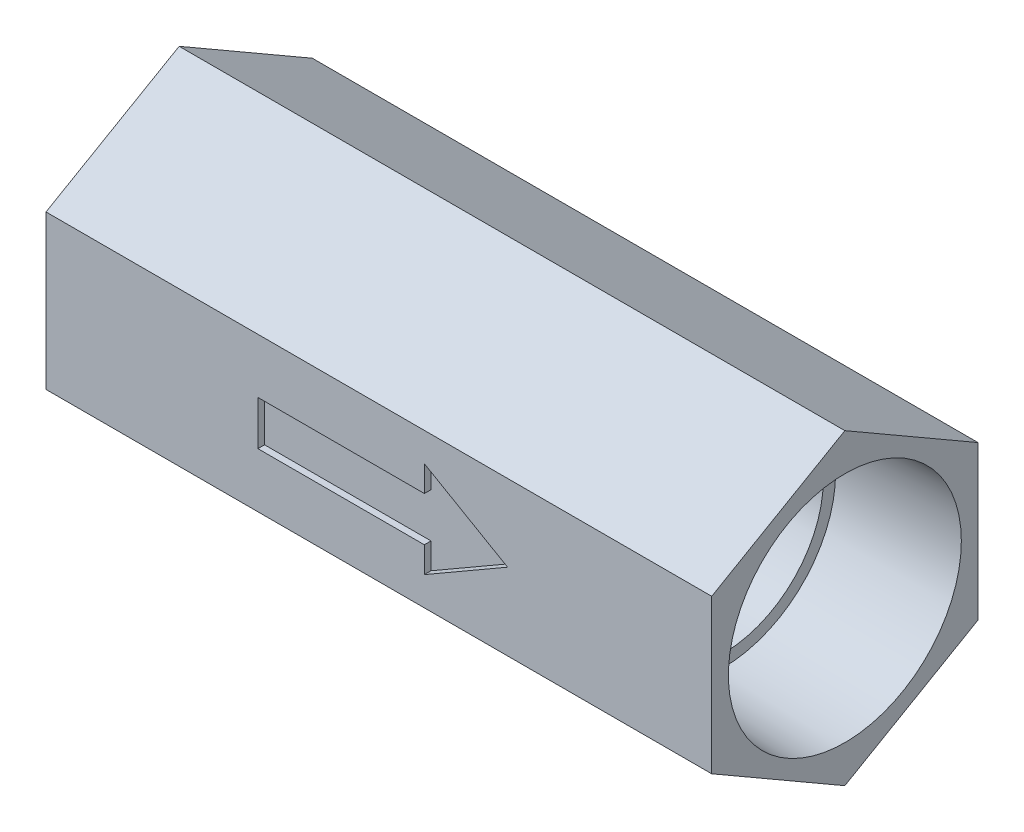
SolidWorks part; units mm, degrees
ref_plane "Front Plane" through (0, 0, 0) normal (0, 0, 1) x (1, 0, 0)
ref_plane "Top Plane" through (0, 0, 0) normal (0, 1, 0) x (1, 0, 0)
ref_plane "Right Plane" through (0, 0, 0) normal (1, 0, 0) x (0, 0, -1)
sketch "Sketch1" plane through (0, 0, 0) normal (1, 0, 0) x (0, 0, -1)
  line L1 (0, 17.5976) -> (-15.24, 8.7988)
  line L2 (-15.24, 8.7988) -> (-15.24, -8.7988)
  line L3 (-15.24, -8.7988) -> (0, -17.5976)
  line L4 (0, -17.5976) -> (15.24, -8.7988)
  line L5 (15.24, -8.7988) -> (15.24, 8.7988)
  line L6 (15.24, 8.7988) -> (0, 17.5976)
  circle A0 centre (0, 0) radius 15.24 construction
  dimension "D1" = 30.48
extrude "Boss-Extrude1" add sketch "Sketch1" along normal blind 38.1 and the other way blind 38.1
sketch "Sketch2" plane through (38.1, 0, 0) normal (1, 0, 0) x (0, 0, -1)
  point P0 (0, 0)
hole_wizard "3/4 NPT Tapped Hole1" positions "Sketch3" profile "Sketch4" size "3/4" standard "ANSI Inch"
sketch "Sketch3" plane through (38.1, 0, 0) normal (1, 0, 0) x (0, 0, -1)
  point P0 (0, 0)
sketch "Sketch4" plane through (38.1, 0, 0) normal (0, 1, 0) x (0, 0, -1)
  line L0 (0, 0) -> (0, 24.6936)
  line L1 (11.5062, 17.78) -> (0, 24.6936)
  line L2 (-11.5062, 17.78) -> (0, 24.6936) construction
  line L3 (11.5062, 17.78) -> (11.5062, 13.97)
  line L4 (11.5062, 13.97) -> (12.9142, 13.97)
  line L5 (12.9142, 13.97) -> (13.3325, 0)
  line L6 (-12.9142, 13.97) -> (-13.3325, 0) construction
  line L7 (13.3325, 0) -> (0, 0)
  line L8 (0, -6.35) -> (0, 107.95) construction
  line L11 (-11.5062, 13.97) -> (-12.9142, 13.97) construction
  dimension "Tap Drill Dia." = 23.0124
  dimension "Tap Drill Depth" = 17.78
  dimension "Thread Dia." = 26.665
  dimension "Thread Angle" = 3.43
  dimension "Thread Depth" = 13.97
  dimension "Drill Angle" = 118
sketch "Sketch5" plane through (-38.1, 0, 0) normal (-1, 0, 0) x (0, 0, 1)
  point P0 (0, 0)
  point P1 (0, 0)
  point P3 (0, 0)
hole_wizard "3/4 NPT Tapped Hole2" positions "Sketch8" profile "Sketch9" size "3/4" standard "ANSI Inch"
sketch "Sketch8" plane through (-38.1, 0, 0) normal (-1, 0, 0) x (0, 0, 1)
  point P0 (0, 0)
sketch "Sketch9" plane through (-38.1, 0, 0) normal (0, 1, 0) x (0, 0, 1)
  line L0 (0, 0) -> (0, 24.6936)
  line L1 (11.5062, 17.78) -> (0, 24.6936)
  line L2 (-11.5062, 17.78) -> (0, 24.6936) construction
  line L3 (11.5062, 17.78) -> (11.5062, 13.97)
  line L4 (11.5062, 13.97) -> (12.9142, 13.97)
  line L5 (12.9142, 13.97) -> (13.3325, 0)
  line L6 (-12.9142, 13.97) -> (-13.3325, 0) construction
  line L7 (13.3325, 0) -> (0, 0)
  line L8 (0, -6.35) -> (0, 107.95) construction
  line L11 (-11.5062, 13.97) -> (-12.9142, 13.97) construction
  dimension "Tap Drill Dia." = 23.0124
  dimension "Tap Drill Depth" = 17.78
  dimension "Thread Dia." = 26.665
  dimension "Thread Angle" = 3.43
  dimension "Thread Depth" = 13.97
  dimension "Drill Angle" = 118
sketch "Sketch10" plane through (0, 0, 15.24) normal (0, 0, 1) x (1, 0, 0)
  line L1 (-13.843, -2.54) -> (5.207, -2.54)
  line L2 (-13.843, -2.54) -> (-13.843, 2.54)
  line L3 (-13.843, 2.54) -> (5.207, 2.54)
  line L4 (5.207, -2.54) -> (5.207, 2.54)
  line L5 (-13.843, -2.54) -> (5.207, 2.54) construction
  line L6 (-13.843, 2.54) -> (5.207, -2.54) construction
  line L7 (14.732, 0) -> (5.207, 5.4993)
  line L8 (5.207, 5.4993) -> (5.207, -5.4993)
  line L9 (5.207, -5.4993) -> (14.732, 0)
  circle A0 centre (8.382, 0) radius 3.175 construction
  point P0 (-4.318, 0)
  point P13 (0, 0)
  dimension "D3" = 6.35
  dimension "D1" = 19.05
  dimension "D2" = 5.08
  dimension "D4" = 4.318
extrude "Cut-Extrude1" cut sketch "Sketch10" against normal blind 0.762 contours L8 L9 L7 L4 | L1 L4 L3 L2 region at (-4.318, 0, 15.24) region at (8.382, 0, 15.24)
sketch "Sketch11" plane through (0, 0, -15.24) normal (0, 0, -1) x (-1, 0, 0)
  text T0 "Check-ALL"
  point P1 (-7.286, -0.751)
  point P2 (-11.9943, -2.5106)
  dimension "D1" = 1.27
  dimension "D2" = 11.43
extrude "Cut-Extrude2" cut sketch "Sketch11" against normal blind 0.762
